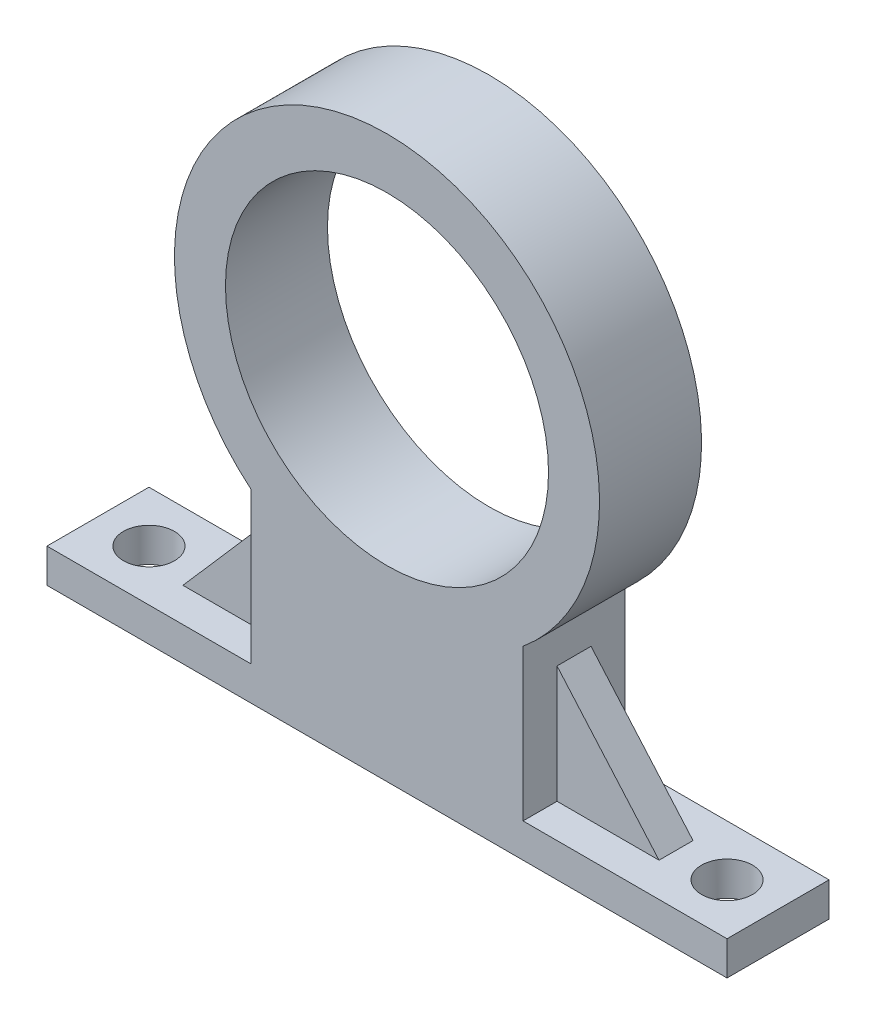
SolidWorks part; units mm, degrees
ref_plane "Front Plane" through (0, 0, 0) normal (0, 0, 1) x (1, 0, 0)
ref_plane "Top Plane" through (0, 0, 0) normal (0, 1, 0) x (1, 0, 0)
ref_plane "Right Plane" through (0, 0, 0) normal (1, 0, 0) x (0, 0, -1)
sketch "Sketch1" plane through (0, 0, 0) normal (0, 0, 1) x (1, 0, 0)
  circle A0 centre (0, 0) radius 9.5
  circle A1 centre (0, 0) radius 12.5
  dimension "D1" = 19
  dimension "D2" = 25
extrude "Boss-Extrude1" add sketch "Sketch1" along normal blind 6
ref_plane "Plane1" through (0, -12.5, 0) normal (0, -1, 0) x (-1, 0, 0)
sketch "Sketch2" plane through (0, -12.5, 0) normal (0, -1, 0) x (-1, 0, 0)
  line L0 (0, -6) -> (0, 0) construction
  line L1 (-12.5, -6) -> (12.5, -6) construction
  line L2 (12.5, -3) -> (-12.5, -3) construction
  line L3 (12.5, -6) -> (12.5, 0) construction
  line L4 (-12.5, 0) -> (-12.5, -6) construction
  line L6 (8, 0) -> (-8, 0)
  line L7 (8, 0) -> (8, -6)
  line L8 (8, -6) -> (-8, -6)
  line L9 (-8, 0) -> (-8, -6)
  line L10 (8, 0) -> (-8, -6) construction
  line L11 (8, -6) -> (-8, 0) construction
  point P11 (0, -3)
  dimension "D1" = 6
  dimension "D2" = 16
extrude "Boss-Extrude2" add sketch "Sketch2" along normal blind 8 and the other way up to next (3 mm away)
sketch "Sketch3" plane through (8, 0, 0) normal (1, 0, 0) x (0, 0, -1)
  line L0 (0, -20.5) -> (0, -9.6047) construction
  line L1 (-6, -20.5) -> (0, -20.5)
  line L2 (-6, -20.5) -> (-6, -18.5)
  line L3 (-6, -18.5) -> (0, -18.5)
  line L4 (0, -20.5) -> (0, -18.5)
  dimension "D1" = 2
extrude "Boss-Extrude3" add sketch "Sketch3" along normal blind 12
mirror "Mirror1" about plane through (0, 0, 0) normal (1, 0, 0) of "Boss-Extrude3"
ref_plane "Plane2" through (0, 0, 3) normal (0, 0, 1) x (1, 0, 0)
sketch "Sketch6" plane through (0, 0, 3) normal (0, 0, 1) x (1, 0, 0)
  line L0 (14, -18.5) -> (8, -11.6047)
  line L1 (20, -18.5) -> (8, -18.5) construction
  line L2 (8, -18.5) -> (8, -9.6047) construction
  line L3 (8, -11.6047) -> (8, -18.5)
  line L4 (8, -18.5) -> (14, -18.5)
  dimension "D1" = 2
extrude "Boss-Extrude4" add sketch "Sketch6" along normal blind 1 and the other way blind 1
mirror "Mirror2" about plane through (0, 0, 0) normal (1, 0, 0) of "Boss-Extrude4"
sketch "Sketch7" plane through (0, -18.5, 0) normal (0, 1, 0) x (1, 0, 0)
  line L0 (-18.15, -3) -> (18.15, -3) construction
  line L1 (-14, -2) -> (-14, -4) construction
  line L2 (0, -3.3) -> (0, 3.3) construction
  circle A0 centre (-17, -3) radius 1.5
  circle A1 centre (17, -3) radius 1.5
  dimension "D1" = 3
  dimension "D2" = 3
extrude "Cut-Extrude1" cut sketch "Sketch7" against normal up to next
ref_axis "Axis1" through (0, 0, 6) along (0, 0, -1)
